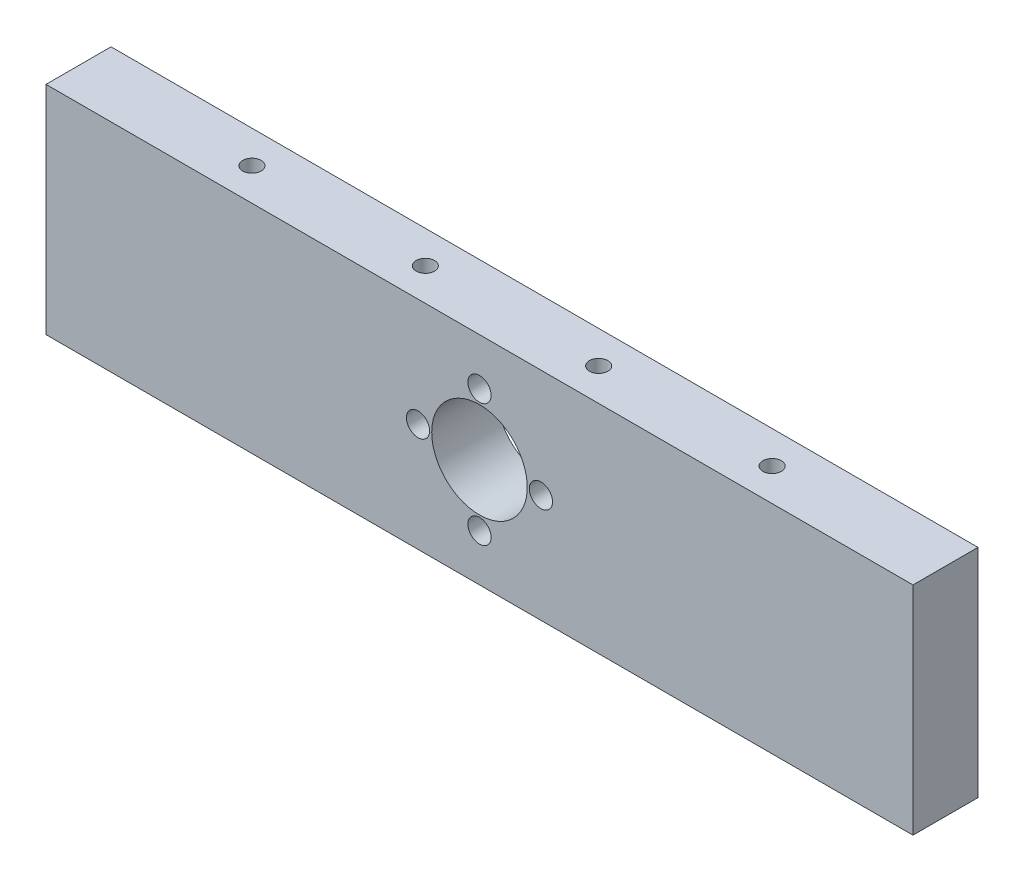
SolidWorks part; units mm, degrees
material "PE High Density Film"
ref_plane "Front Plane" through (0, 0, 0) normal (0, 0, 1) x (1, 0, 0)
ref_plane "Top Plane" through (0, 0, 0) normal (0, 1, 0) x (1, 0, 0)
ref_plane "Right Plane" through (0, 0, 0) normal (1, 0, 0) x (0, 0, -1)
sketch "Sketch1" plane through (0, 0, 0) normal (0, 0, 1) x (1, 0, 0)
  line L1 (-63.5, 15.875) -> (63.5, 15.875)
  line L2 (-63.5, 15.875) -> (-63.5, -15.875)
  line L3 (-63.5, -15.875) -> (63.5, -15.875)
  line L4 (63.5, 15.875) -> (63.5, -15.875)
  circle A0 centre (0, -9) radius 1.7
  circle A1 centre (-9, 0) radius 1.7
  circle A2 centre (0, 9) radius 1.7
  circle A3 centre (9, 0) radius 1.7
  arc A8 (-5.3578, -2.967) -> (-5.3172, -2.9531) centre (-6.35, 0) ccw construction
  circle A16 centre (0, 0) radius 7
  circle A17 centre (0, 0) radius 9 construction
  point P0 (0, 0)
  dimension "D3" = 3.4
  dimension "D5" = 14
  dimension "D1" = 127
  dimension "D2" = 31.75
  dimension "D8" = 127
  dimension "D11" = 9
  dimension "D4" = 63.5
extrude "Boss-Extrude1" add sketch "Sketch1" along normal blind 9.525
hole_wizard "Tap Drill for #6-32 Tap1" positions "Sketch11" profile "Sketch12" hole size "#6-32" standard "ANSI Inch"
sketch "Sketch11" plane through (0, -15.875, 0) normal (0, -1, 0) x (-1, 0, 0)
  line L0 (-63.5, -9.525) -> (-63.5, 0) construction
  line L1 (63.5, -9.525) -> (-63.5, -9.525) construction
  point P0 (-38.1, -4.7625)
  dimension "D1" = 25.4
  dimension "D2" = 4.7625
sketch "Sketch12" plane through (38.1, -15.875, 4.7625) normal (1, 0, 0) x (0, 0, -1)
  line L0 (0, 0) -> (0, 13.5127)
  line L1 (0, 13.5127) -> (1.3525, 12.7)
  line L2 (1.3525, 12.7) -> (1.3525, 0)
  line L5 (1.3525, 0) -> (0, 0)
  line L10 (0, 13.5127) -> (-1.3526, 12.7) construction
  line L11 (0, -6.35) -> (0, 107.95) construction
  dimension "Hole Dia." = 2.7051
  dimension "Hole Depth" = 12.7
  dimension "Drill Angle" = 118
pattern_linear "LPattern1" count 4 spacing 25.4 along (-1, 0, 0) of "Tap Drill for #6-32 Tap1"
mirror "Mirror8" about plane through (0, 0, 0) normal (0, 1, 0) of "Tap Drill for #6-32 Tap1", "LPattern1"
equation "\"Plate Screw Hole Diameter\"= 0.116in"
equation "\"Plate Width\" = 5in"
equation "\"Plate Thickness\" = 0.375in"
equation "\"Num holes\" = 4"
equation "\"Plate Height\" = 1.25in"
equation "\"D1@Sketch11\"=\"Plate Width\" / ( \"Num holes\" + 1)"
equation "\"D2@Sketch11\"=\"Plate Thickness\"/2"
equation "\"D3@LPattern1\"=\"Plate Width\" / ( \"Num holes\"  + 1 )"
equation "\"D1@Sketch1\"=\"Plate Width\""
equation "\"D2@Sketch1\"=\"Plate Height\""
equation "\"D4@Sketch1\"= \"Plate Width\"/2"
equation "\"Top Plate Width\" = 5in"
equation "\"D8@Sketch1\"=\"Top Plate WIdth\""
